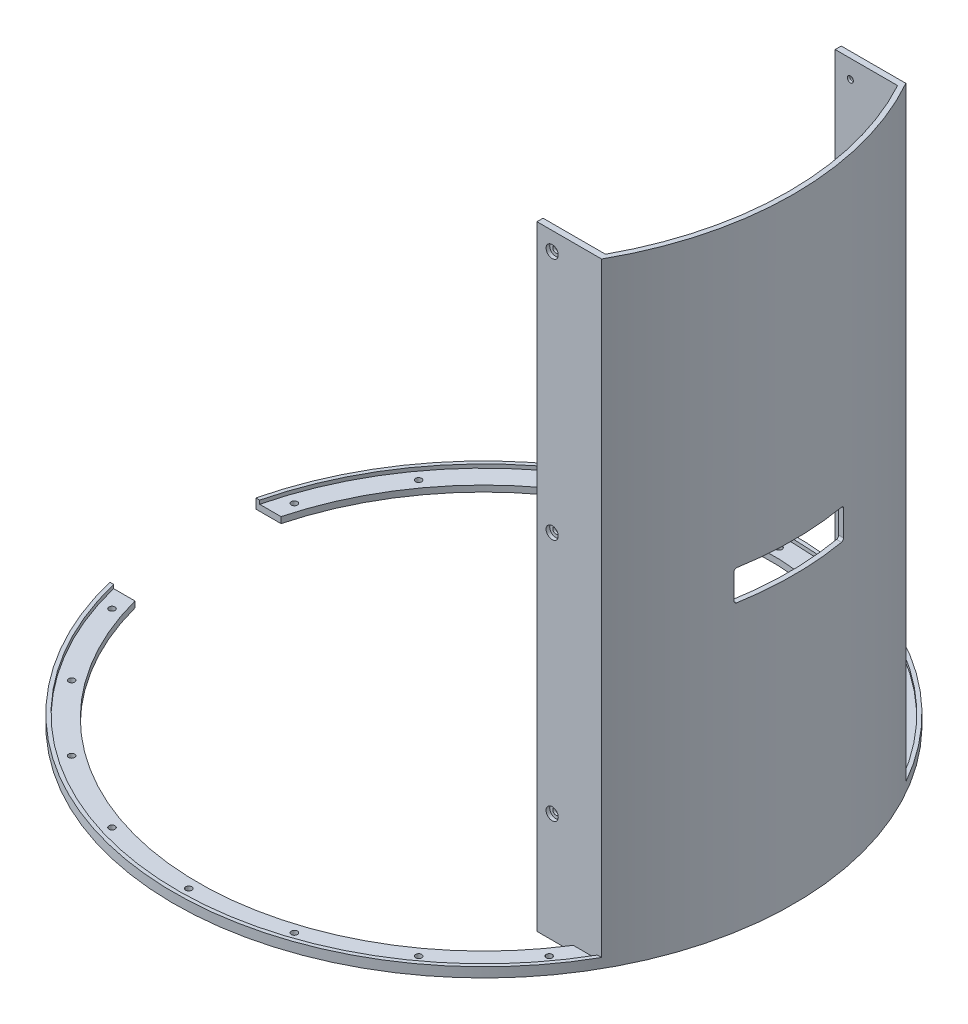
SolidWorks part; units mm, degrees
ref_plane "Front Plane" through (0, 0, 0) normal (0, 0, 1) x (1, 0, 0)
ref_plane "Top Plane" through (0, 0, 0) normal (0, 1, 0) x (1, 0, 0)
ref_plane "Right Plane" through (0, 0, 0) normal (1, 0, 0) x (0, 0, -1)
sketch "Sketch1" plane through (0, 0, 0) normal (0, 1, 0) x (1, 0, 0)
  circle A0 centre (0, 0) radius 254.5
  circle A1 centre (0, 0) radius 234.5
  dimension "D1" = 20
extrude "Boss-Extrude1" add sketch "Sketch1" along normal blind 5
sketch "Sketch2" plane through (0, 5, 0) normal (0, 1, 0) x (1, 0, 0)
  line L0 (254.5, 0) -> (234.5, 0)
  line L1 (221.6873, 125) -> (198.4068, 125)
  line L3 (168.5, 125) -> (165.5, 125) construction
  arc A0 (254.5, 0) -> (221.6873, 125) centre (0, 0) ccw
  circle A2 centre (0, 0) radius 254.5 construction
  circle A7 centre (0, 0) radius 234.5 construction
  arc A8 (198.4068, 125) -> (234.5, 0) centre (0, 0) cw
  circle M1 centre (0, 0) radius 254.5
  circle M2 centre (0, 0) radius 234.5
  dimension "D1" = 0
  dimension "D2" = 0
extrude "Boss-Extrude2" add sketch "Sketch2" along normal blind 500 contours L1 M1 M2 region at (232.9072, 5, -64.0481)
mirror "Mirror1" about plane through (0, 505, 0) normal (0, 0, 1) of "Boss-Extrude2"
sketch "Sketch3" plane through (0, 5, 0) normal (0, 1, 0) x (1, 0, 0)
  line L1 (-254.5, 0) -> (-226.6942, 0)
  line L2 (-254.5, 0) -> (-254.5, 60)
  line L3 (-254.5, 60) -> (-226.6942, 60)
  line L4 (-226.6942, 0) -> (-226.6942, 60)
  arc A0 (221.6873, 125) -> (221.6873, -125) centre (0, 0) ccw construction
  arc A1 (198.4068, 125) -> (198.4068, -125) centre (0, 0) ccw construction
  dimension "D1" = 60
extrude "Cut-Extrude1" cut sketch "Sketch3" against normal blind 500
mirror "Mirror2" about plane through (0, 0, 0) normal (0, 0, 1) of "Cut-Extrude1"
sketch "Sketch4" plane through (0, 505, 0) normal (0, 1, 0) x (1, 0, 0)
  circle A0 centre (0, 0) radius 250.5
  arc A1 (221.6873, -125) -> (221.6873, 125) centre (0, 0) ccw construction
  dimension "D1" = 4
extrude "Cut-Extrude2" cut sketch "Sketch4" against normal blind 500
sketch "Sketch8" plane through (0, 5, 0) normal (0, 1, 0) x (1, 0, 0)
  line L0 (217.0835, 125) -> (168.5835, 125)
  line L1 (168.5835, 125) -> (168.5835, 120)
  line L2 (168.5835, 120) -> (220.0458, 120)
  line L3 (220.0458, 120) -> (220.0458, 125)
  line L4 (221.6873, 125) -> (217.0835, 125) construction
  line L5 (220.0458, 125) -> (217.0835, 125)
  dimension "D1" = 5
  dimension "D2" = 48.5
extrude "Boss-Extrude3" add sketch "Sketch8" along normal blind 500
mirror "Mirror3" about plane through (0, 0, 0) normal (0, 0, 1) of "Boss-Extrude3"
sketch "Sketch10" plane through (0, 0, 0) normal (0, -1, 0) x (1, 0, 0)
  line L0 (168.5835, 125) -> (168.5835, -125)
  line L1 (168.5835, 125) -> (208.5835, 125)
  line L2 (168.5835, -125) -> (208.5835, -125)
  arc A3 (208.5835, 125) -> (208.5835, -125) centre (0, 0) cw
  arc M3 (-226.6942, 60) -> (-226.6942, -60) centre (0, 0) cw
extrude "Boss-Extrude4" add sketch "Sketch10" against normal blind 5 contours L0 L2 L1 M3 region at (196.7643, 0, 0)
sketch "Sketch11" plane through (0, 5, 0) normal (0, 1, 0) x (1, 0, 0)
  line L0 (168.5835, -120) -> (168.5835, 120) construction
  line L1 (168.5835, 93.5) -> (190, 93.5)
  line L2 (168.5835, 93.5) -> (168.5835, -96.5)
  line L3 (168.5835, -96.5) -> (190, -96.5)
  line L4 (190, 93.5) -> (190, -96.5)
  line L5 (188.5, -95) -> (188.5, -75) construction
  line L6 (168.5, -95) -> (188.5, -95) construction
  line L7 (188.5, 95) -> (168.5, 95) construction
  point P10 (178.5, -95)
  dimension "D1" = 1.5
  dimension "D2" = 1.5
  dimension "D3" = 1.5
extrude "Cut-Extrude3" cut sketch "Sketch11" against normal blind 10
sketch "Sketch12" plane through (0, 5, 0) normal (0, 1, 0) x (1, 0, 0)
  line L0 (-2.75, 0) -> (2.75, 0) construction
  line L1 (168.5835, 120) -> (185, 120)
  line L2 (168.5835, 120) -> (168.5835, 93.5)
  line L3 (168.5835, 93.5) -> (190, 93.5)
  line L4 (190, 115) -> (190, 93.5)
  line L5 (190, 93.5) -> (213, 93.5)
  line L6 (190, 93.5) -> (190, 75)
  line L7 (190, 75) -> (213, 75)
  line L8 (218, 88.5) -> (218, 80)
  line L9 (218, -88.5) -> (218, -80)
  line L10 (190, -75) -> (213, -75)
  line L11 (190, -93.5) -> (190, -75)
  line L12 (190, -93.5) -> (213, -93.5)
  line L13 (190, -115) -> (190, -93.5)
  line L14 (168.5835, -93.5) -> (190, -93.5)
  line L15 (168.5835, -120) -> (168.5835, -93.5)
  line L16 (168.5835, -120) -> (185, -120)
  arc A0 (213, -93.5) -> (218, -88.5) centre (213, -88.5) ccw
  arc A1 (218, -80) -> (213, -75) centre (213, -80) ccw
  arc A2 (190, -115) -> (185, -120) centre (185, -115) cw
  arc A3 (213, 75) -> (218, 80) centre (213, 80) ccw
  arc A4 (218, 88.5) -> (213, 93.5) centre (213, 88.5) ccw
  arc A5 (190, 115) -> (185, 120) centre (185, 115) ccw
  point P20 (218, -93.5)
  point P23 (218, -75)
  point P26 (190, -120)
  point P29 (218, 75)
  point P32 (218, 93.5)
  point P35 (190, 120)
  line M3 (190, 93.5) -> (190, -96.5)
  line M4 (190, -96.5) -> (168.5835, -96.5)
  line M5 (168.5835, -96.5) -> (168.5835, -120)
  line M6 (168.5835, -120) -> (219.8869, -120)
  dimension "D2" = 5
  dimension "D1" = 28
extrude "Cut-Extrude4" cut sketch "Sketch12" against normal blind 10 contours L8 L5 L7 M3 | L9 A1 L10 L12 A0 M3 | A2 L13 M4 M5 M6 | L4 A5 L1 L2 L3 region at (203.7275, 5, 84.25) region at (203.7275, 5, -84.25) region at (179.1884, 5, 108.1354)
fillet "Fillet1" radius 5 4 edges at (190, 2.5, 93.5) (190, 2.5, -93.5) (190, 2.5, -75) (190, 2.5, 75)
sketch "Sketch15" plane through (0, 5, 0) normal (0, 1, 0) x (1, 0, 0)
  circle A0 centre (242.5, 0) radius 2.5
  circle A1 centre (196.1866, -142.5379) radius 2.5
  circle A2 centre (74.9366, -230.6312) radius 2.5
  circle A3 centre (-74.9366, -230.6312) radius 2.5
  circle A4 centre (-196.1866, -142.5379) radius 2.5
  circle A5 centre (-242.5, 0) radius 2.5
  circle A6 centre (-196.1866, 142.5379) radius 2.5
  circle A7 centre (-74.9366, 230.6312) radius 2.5
  circle A8 centre (74.9366, 230.6312) radius 2.5
  circle A9 centre (196.1866, 142.5379) radius 2.5
  point P23 (0, 0)
  dimension "D1" = 242.5
  dimension "D2" = 10
extrude "Cut-Extrude5" cut sketch "Sketch15" against normal blind 10
sketch "Sketch16" plane through (0, 5, 0) normal (0, 1, 0) x (1, 0, 0)
  line L0 (-226.6942, 60) -> (-247.3262, 60) construction
  line L1 (221.6873, 125) -> (198.4068, 125) construction
  line L2 (-247.3262, 60) -> (-244.2381, 60)
  line L3 (221.6873, 125) -> (218.2367, 125)
  line L4 (-2.75, 0) -> (2.75, 0) construction
  line L5 (221.6873, -125) -> (218.2367, -125)
  line L6 (-247.3262, -60) -> (-244.2381, -60)
  arc A0 (221.6873, 125) -> (-247.3262, 60) centre (0, 0) ccw
  arc A1 (218.2367, 125) -> (-244.2381, 60) centre (0, 0) ccw
  arc A2 (218.2367, -125) -> (-244.2381, -60) centre (0, 0) cw
  arc A3 (221.6873, -125) -> (-247.3262, -60) centre (0, 0) cw
  dimension "D1" = 3
extrude "Boss-Extrude5" add sketch "Sketch16" along normal blind 3
sketch "Sketch18" plane through (0, 5, 0) normal (0, 1, 0) x (1, 0, 0)
  circle A0 centre (0, -242.5) radius 2.5
  circle A1 centre (-142.5379, -196.1866) radius 2.5
  circle A2 centre (-230.6312, -74.9366) radius 2.5
  circle A3 centre (-230.6312, 74.9366) radius 2.5
  circle A4 centre (-142.5379, 196.1866) radius 2.5
  circle A5 centre (0, 242.5) radius 2.5
  circle A6 centre (142.5379, 196.1866) radius 2.5
  circle A7 centre (230.6312, 74.9366) radius 2.5
  circle A8 centre (230.6312, -74.9366) radius 2.5
  circle A9 centre (142.5379, -196.1866) radius 2.5
  point P23 (0, 0)
  dimension "D1" = 242.5
  dimension "D2" = 10
extrude "Cut-Extrude6" cut sketch "Sketch18" against normal blind 5
sketch "Sketch19" plane through (0, 0, 0) normal (0, -1, 0) x (1, 0, 0)
  line L1 (193, 20) -> (207, 20)
  line L2 (190, 17) -> (190, -17)
  line L3 (193, -20) -> (207, -20)
  line L4 (210, 17) -> (210, -17)
  line L5 (193, -20) -> (190, -20)
  line L7 (190, -20) -> (190, -17)
  line L8 (193, 20) -> (190, 20)
  line L9 (190, 20) -> (190, 17)
  arc A1 (207, -20) -> (210, -17) centre (207, -17) ccw
  arc A2 (210, 17) -> (207, 20) centre (207, 17) ccw
  point P14 (190, 20)
extrude "Cut-Extrude7" cut sketch "Sketch19" against normal blind 7
fillet "Fillet2" radius 5 2 edges at (190, 2.5, 20) (190, 2.5, -20)
sketch "Sketch21" plane through (0, 5, 0) normal (0, 1, 0) x (1, 0, 0)
  line L0 (207, 20) -> (195, 20) construction
  line L1 (195, -20) -> (207, -20) construction
  line L2 (190, 25) -> (190, 70) construction
  line L3 (190, -70) -> (190, -25) construction
  circle A0 centre (200, 50) radius 2.5
  circle A1 centre (200, -50) radius 2.5
  dimension "D1" = 30
  dimension "D2" = 30
  dimension "D3" = 10
  dimension "D4" = 10
extrude "Cut-Extrude8" cut sketch "Sketch21" against normal blind 10
sketch "Sketch22" plane through (0, 0, 125) normal (0, 0, 1) x (1, 0, 0)
  line L0 (168.5835, 505) -> (168.5835, 0) construction
  line L1 (221.6873, 505) -> (168.5835, 505) construction
  circle A0 centre (181.0835, 490) radius 2.5
  circle A1 centre (181.0835, 290) radius 2.5
  circle A2 centre (181.0835, 90) radius 2.5
  dimension "D1" = 12.5
  dimension "D2" = 15
  dimension "D3" = 3
extrude "Cut-Extrude9" cut sketch "Sketch22" against normal blind 14
mirror "Mirror4" about plane through (0, 0, 0) normal (0, 0, 1) of "Cut-Extrude9"
sketch "Sketch23" plane through (0, 0, 125) normal (0, 0, 1) x (1, 0, 0)
  circle A0 centre (181.0835, 490) radius 5
  circle A1 centre (181.0835, 290) radius 5
  circle A2 centre (181.0835, 90) radius 5
  dimension "D1" = 3
extrude "Cut-Extrude10" cut sketch "Sketch23" against normal blind 3
mirror "Mirror5" about plane through (0, 0, 0) normal (0, 0, 1) of "Cut-Extrude10"
sketch "Sketch24" plane through (0, 0, 0) normal (0, 0, 1) x (1, 0, 0)
  line L0 (254.5, 0) -> (254.5, 505) construction
  line L1 (268.5989, 234) -> (240.4011, 234)
  line L2 (268.5989, 234) -> (268.5989, 259)
  line L3 (268.5989, 259) -> (240.4011, 259)
  line L4 (240.4011, 234) -> (240.4011, 259)
  line L5 (268.5989, 234) -> (240.4011, 259) construction
  line L6 (268.5989, 259) -> (240.4011, 234) construction
  line L7 (221.6873, 8) -> (-247.3262, 8) construction
  point P0 (254.5, 246.5)
  dimension "D1" = 226
  dimension "D2" = 25
extrude "Cut-Extrude11" cut sketch "Sketch24" against normal mid plane 90
fillet "Fillet3" radius 2 4 edges at (248.4575, 259, 45) (248.4575, 234, 45) (248.4575, 234, -45) (248.4575, 259, -45)
